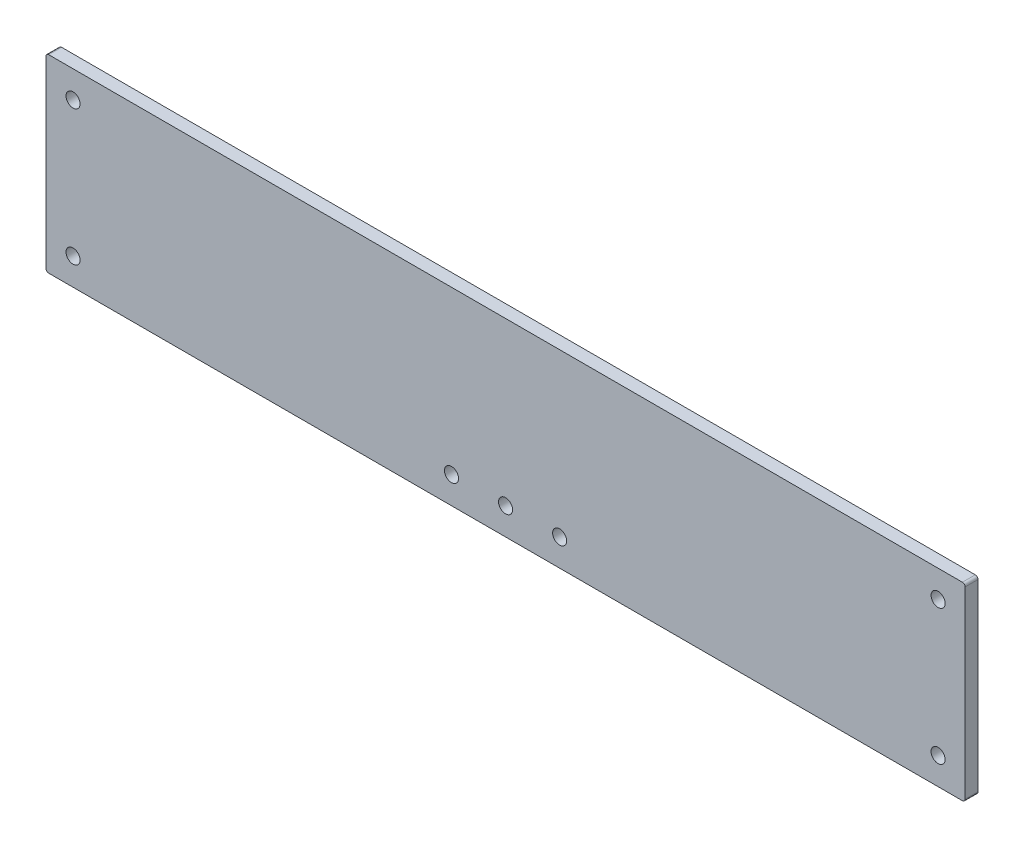
SolidWorks part; units mm, degrees
ref_plane "Front Plane" through (0, 0, 0) normal (0, 0, 1) x (1, 0, 0)
ref_plane "Top Plane" through (0, 0, 0) normal (0, 1, 0) x (1, 0, 0)
ref_plane "Right Plane" through (0, 0, 0) normal (1, 0, 0) x (0, 0, -1)
ref_plane "Plane1" through (0, 0, 4.7625) normal (0, 0, 1) x (1, 0, 0)
sketch "Sketch11" plane through (0, 0, 4.7625) normal (0, 0, 1) x (1, 0, 0)
  line L0 (0, 69) -> (0, 1)
  line L1 (1, 0) -> (339, 0)
  line L2 (340, 1) -> (340, 69)
  line L3 (339, 70) -> (1, 70)
  arc A0 (1, 70) -> (0, 69) centre (1, 69) ccw
  arc A1 (0, 1) -> (1, 0) centre (1, 1) ccw
  arc A2 (339, 0) -> (340, 1) centre (339, 1) ccw
  arc A3 (340, 69) -> (339, 70) centre (339, 69) ccw
base flange "Base-Flange1" sketch "Sketch11" thickness 4.7625 reverse thickness direction yes parameters "D1"=0
hole_wizard "Ø5.2 (5.2) Diameter Hole1" positions "Sketch17" profile "Sketch16" hole size "Ø5.2" standard "ANSI Metric"
sketch "Sketch17" plane through (0, 0, 4.7625) normal (0, 0, 1) x (1, 0, 0)
  point P0 (190, 10)
  point P1 (170, 10)
  point P2 (330, 60)
  point P3 (10, 10)
  point P4 (10, 60)
  point P5 (330, 10)
  point P6 (150, 10)
sketch "Sketch16" plane through (190, 10, 4.7625) normal (1, 0, 0) x (0, -1, 0)
  line L0 (0, 0) -> (0, 4.7625)
  line L1 (0, 4.7625) -> (2.6, 4.7625)
  line L2 (2.6, 4.7625) -> (2.6, 0)
  line L5 (2.6, 0) -> (0, 0)
  line L11 (0, -6.35) -> (0, 107.95) construction
  dimension "Thru Hole Dia." = 5.2
  dimension "Thru Hole Depth" = 4.7625
sketch "Bend-Lines4" plane through (0, 0, 0) normal (0, 1, 0) x (1, 0, 0)
sketch "Bounding-Box4" plane through (0, 0, 0) normal (0, 1, 0) x (1, 0, 0)
sheet metal parameters "Sheet-Metal(5)" thickness 4.7625 parameters "D1"=0
flat pattern "Flat-Pattern(5)" [suppressed]
sketch "Bend-Lines5" plane through (0, 0, 0) normal (0, 1, 0) x (1, 0, 0)
sketch "Bounding-Box5" [suppressed] plane through (0, 0, 0) normal (0, 1, 0) x (1, 0, 0)
sheet metal parameters "Sheet-Metal(6)" thickness 4.7625 parameters "D1"=0
flat pattern "Flat-Pattern(5)"
sketch "Bend-Lines5" plane through (0, 0, 0) normal (0, 1, 0) x (1, 0, 0)
sketch "Bounding-Box5" [suppressed] plane through (0, 0, 0) normal (0, 1, 0) x (1, 0, 0)
